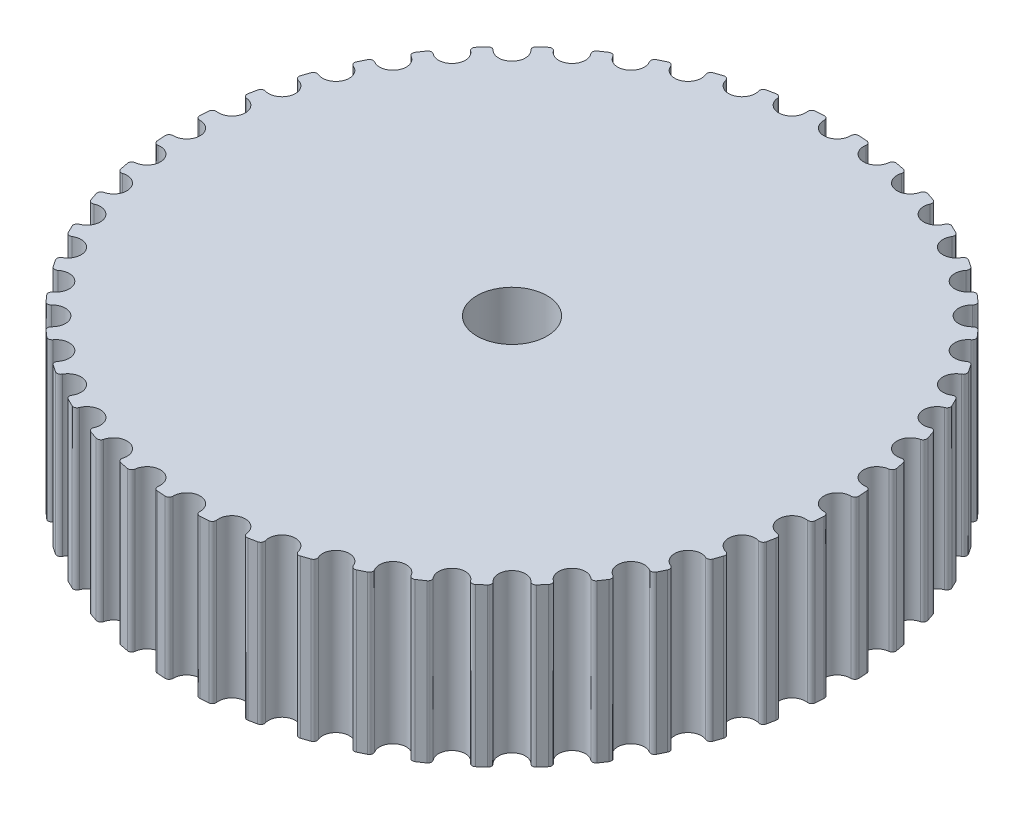
SolidWorks part; units mm, degrees
ref_plane "Ebene vorne" through (0, 0, 0) normal (0, 0, 1) x (1, 0, 0)
ref_plane "Ebene oben" through (0, 0, 0) normal (0, 1, 0) x (1, 0, 0)
ref_plane "Ebene rechts" through (0, 0, 0) normal (1, 0, 0) x (0, 0, -1)
sketch "Skizze1" plane through (0, 0, 0) normal (0, 1, 0) x (1, 0, 0)
  line L0 (0, 0) -> (27482.8107, 0) construction
  line L1 (0, 0) -> (0, 27482.8107) construction
  line L2 (0, 0) -> (8.3206, 63.2012) construction
  line L3 (1.9824, 37.5727) -> (2.9388, 37.51)
  line L4 (6.8697, 36.9925) -> (7.8097, 36.8055)
  line L5 (11.6394, 35.7794) -> (12.547, 35.4713)
  line L6 (16.2099, 33.954) -> (17.0696, 33.5301)
  line L7 (20.5032, 31.5477) -> (21.3001, 31.0152)
  line L8 (24.4455, 28.6016) -> (25.1662, 27.9697)
  line L9 (27.9697, 25.1662) -> (28.6016, 24.4455)
  line L10 (31.0152, 21.3001) -> (31.5477, 20.5032)
  line L11 (33.5301, 17.0696) -> (33.954, 16.2099)
  line L12 (35.4713, 12.547) -> (35.7794, 11.6394)
  line L13 (36.8055, 7.8097) -> (36.9925, 6.8697)
  line L14 (37.51, 2.9388) -> (37.5727, 1.9824)
  line L15 (37.5727, -1.9824) -> (37.51, -2.9388)
  line L16 (36.9925, -6.8697) -> (36.8055, -7.8097)
  line L17 (35.7794, -11.6394) -> (35.4713, -12.547)
  line L18 (33.954, -16.2099) -> (33.5301, -17.0696)
  line L19 (31.5477, -20.5032) -> (31.0152, -21.3001)
  line L20 (28.6016, -24.4455) -> (27.9697, -25.1662)
  line L21 (25.1662, -27.9697) -> (24.4455, -28.6016)
  line L22 (21.3001, -31.0152) -> (20.5032, -31.5477)
  line L23 (17.0696, -33.5301) -> (16.2099, -33.954)
  line L24 (12.547, -35.4713) -> (11.6394, -35.7794)
  line L25 (7.8097, -36.8055) -> (6.8697, -36.9925)
  line L26 (2.9388, -37.51) -> (1.9824, -37.5727)
  line L27 (-1.9824, -37.5727) -> (-2.9388, -37.51)
  line L28 (-6.8697, -36.9925) -> (-7.8097, -36.8055)
  line L29 (-11.6394, -35.7794) -> (-12.547, -35.4713)
  line L30 (-16.2099, -33.954) -> (-17.0696, -33.5301)
  line L31 (-20.5032, -31.5477) -> (-21.3001, -31.0152)
  line L32 (-24.4455, -28.6016) -> (-25.1662, -27.9697)
  line L33 (-27.9697, -25.1662) -> (-28.6016, -24.4455)
  line L34 (-31.0152, -21.3001) -> (-31.5477, -20.5032)
  line L35 (-33.5301, -17.0696) -> (-33.954, -16.2099)
  line L36 (-35.4713, -12.547) -> (-35.7794, -11.6394)
  line L37 (-36.8055, -7.8097) -> (-36.9925, -6.8697)
  line L38 (-37.51, -2.9388) -> (-37.5727, -1.9824)
  line L39 (-37.5727, 1.9824) -> (-37.51, 2.9388)
  line L40 (-36.9925, 6.8697) -> (-36.8055, 7.8097)
  line L41 (-35.7794, 11.6394) -> (-35.4713, 12.547)
  line L42 (-33.954, 16.2099) -> (-33.5301, 17.0696)
  line L43 (-31.5477, 20.5032) -> (-31.0152, 21.3001)
  line L44 (-28.6016, 24.4455) -> (-27.9697, 25.1662)
  line L45 (-25.1662, 27.9697) -> (-24.4455, 28.6016)
  line L46 (-21.3001, 31.0152) -> (-20.5032, 31.5477)
  line L47 (-17.0696, 33.5301) -> (-16.2099, 33.954)
  line L48 (-12.547, 35.4713) -> (-11.6394, 35.7794)
  line L49 (-7.8097, 36.8055) -> (-6.8697, 36.9925)
  line L50 (-2.9388, 37.51) -> (-1.9824, 37.5727)
  circle A0 centre (0, 0) radius 37.625 construction
  circle A1 centre (0, 0) radius 35.565 construction
  arc A2 (0, 35.565) -> (1.5244, 37.1318) centre (0, 37.09) ccw
  arc A3 (1.9824, 37.5727) -> (1.5244, 37.1318) centre (1.9543, 37.1436) ccw
  arc A4 (3.3353, 37.0131) -> (4.6422, 35.2607) centre (4.8412, 36.7727) ccw
  arc A5 (3.3353, 37.0131) -> (2.9388, 37.51) centre (2.9107, 37.0809) ccw
  arc A6 (8.1379, 36.2611) -> (9.2049, 34.3532) centre (9.5996, 35.8262) ccw
  arc A7 (8.1379, 36.2611) -> (7.8097, 36.8055) centre (7.7258, 36.3838) ccw
  arc A8 (6.8697, 36.9925) -> (6.3581, 36.6152) centre (6.7858, 36.5708) ccw
  arc A9 (4.6422, 35.2607) -> (6.3581, 36.6152) centre (4.8412, 36.7727) ccw
  arc A10 (12.8014, 34.8887) -> (13.6101, 32.8578) centre (14.1937, 34.2667) ccw
  arc A11 (12.8014, 34.8887) -> (12.547, 35.4713) centre (12.4087, 35.0641) ccw
  arc A12 (11.6394, 35.7794) -> (11.0829, 35.472) centre (11.5012, 35.3722) ccw
  arc A13 (9.2049, 34.3532) -> (11.0829, 35.472) centre (9.5996, 35.8262) ccw
  arc A14 (17.2457, 32.9193) -> (17.7825, 30.8002) centre (18.545, 32.1209) ccw
  arc A15 (17.2457, 32.9193) -> (17.0696, 33.5301) centre (16.8794, 33.1445) ccw
  arc A16 (16.2099, 33.954) -> (15.6181, 33.722) centre (16.0198, 33.5684) ccw
  arc A17 (13.6101, 32.8578) -> (15.6181, 33.722) centre (14.1937, 34.2667) ccw
  arc A18 (21.395, 30.3867) -> (21.6506, 28.2156) centre (22.579, 29.4255) ccw
  arc A19 (21.395, 30.3867) -> (21.3001, 31.0152) centre (21.0612, 30.6577) ccw
  arc A20 (20.5032, 31.5477) -> (19.8861, 31.3949) centre (20.2643, 31.1902) ccw
  arc A21 (17.7825, 30.8002) -> (19.8861, 31.3949) centre (18.545, 32.1209) ccw
  arc A22 (25.1782, 27.3341) -> (25.1483, 25.1483) centre (26.2266, 26.2266) ccw
  arc A23 (25.1782, 27.3341) -> (25.1662, 27.9697) centre (24.8826, 27.6464) ccw
  arc A24 (24.4455, 28.6016) -> (23.8138, 28.5306) centre (24.162, 28.2783) ccw
  arc A25 (21.6506, 28.2156) -> (23.8138, 28.5306) centre (22.579, 29.4255) ccw
  arc A26 (28.5306, 23.8138) -> (28.2156, 21.6506) centre (29.4255, 22.579) ccw
  arc A27 (28.5306, 23.8138) -> (28.6016, 24.4455) centre (28.2783, 24.162) ccw
  arc A28 (27.9697, 25.1662) -> (27.3341, 25.1782) centre (27.6464, 24.8826) ccw
  arc A29 (25.1483, 25.1483) -> (27.3341, 25.1782) centre (26.2266, 26.2266) ccw
  arc A30 (31.3949, 19.8861) -> (30.8002, 17.7825) centre (32.1209, 18.545) ccw
  arc A31 (31.3949, 19.8861) -> (31.5477, 20.5032) centre (31.1902, 20.2643) ccw
  arc A32 (31.0152, 21.3001) -> (30.3867, 21.395) centre (30.6577, 21.0612) ccw
  arc A33 (28.2156, 21.6506) -> (30.3867, 21.395) centre (29.4255, 22.579) ccw
  arc A34 (33.722, 15.6181) -> (32.8578, 13.6101) centre (34.2667, 14.1937) ccw
  arc A35 (33.722, 15.6181) -> (33.954, 16.2099) centre (33.5684, 16.0198) ccw
  arc A36 (33.5301, 17.0696) -> (32.9193, 17.2457) centre (33.1445, 16.8794) ccw
  arc A37 (30.8002, 17.7825) -> (32.9193, 17.2457) centre (32.1209, 18.545) ccw
  arc A38 (35.472, 11.0829) -> (34.3532, 9.2049) centre (35.8262, 9.5996) ccw
  arc A39 (35.472, 11.0829) -> (35.7794, 11.6394) centre (35.3722, 11.5012) ccw
  arc A40 (35.4713, 12.547) -> (34.8887, 12.8014) centre (35.0641, 12.4087) ccw
  arc A41 (32.8578, 13.6101) -> (34.8887, 12.8014) centre (34.2667, 14.1937) ccw
  arc A42 (36.6152, 6.3581) -> (35.2607, 4.6422) centre (36.7727, 4.8412) ccw
  arc A43 (36.6152, 6.3581) -> (36.9925, 6.8697) centre (36.5708, 6.7858) ccw
  arc A44 (36.8055, 7.8097) -> (36.2611, 8.1379) centre (36.3838, 7.7258) ccw
  arc A45 (34.3532, 9.2049) -> (36.2611, 8.1379) centre (35.8262, 9.5996) ccw
  arc A46 (37.1318, 1.5244) -> (35.565, 0) centre (37.09, 0) ccw
  arc A47 (37.1318, 1.5244) -> (37.5727, 1.9824) centre (37.1436, 1.9543) ccw
  arc A48 (37.51, 2.9388) -> (37.0131, 3.3353) centre (37.0809, 2.9107) ccw
  arc A49 (35.2607, 4.6422) -> (37.0131, 3.3353) centre (36.7727, 4.8412) ccw
  arc A50 (37.0131, -3.3353) -> (35.2607, -4.6422) centre (36.7727, -4.8412) ccw
  arc A51 (37.0131, -3.3353) -> (37.51, -2.9388) centre (37.0809, -2.9107) ccw
  arc A52 (37.5727, -1.9824) -> (37.1318, -1.5244) centre (37.1436, -1.9543) ccw
  arc A53 (35.565, 0) -> (37.1318, -1.5244) centre (37.09, 0) ccw
  arc A54 (36.2611, -8.1379) -> (34.3532, -9.2049) centre (35.8262, -9.5996) ccw
  arc A55 (36.2611, -8.1379) -> (36.8055, -7.8097) centre (36.3838, -7.7258) ccw
  arc A56 (36.9925, -6.8697) -> (36.6152, -6.3581) centre (36.5708, -6.7858) ccw
  arc A57 (35.2607, -4.6422) -> (36.6152, -6.3581) centre (36.7727, -4.8412) ccw
  arc A58 (34.8887, -12.8014) -> (32.8578, -13.6101) centre (34.2667, -14.1937) ccw
  arc A59 (34.8887, -12.8014) -> (35.4713, -12.547) centre (35.0641, -12.4087) ccw
  arc A60 (35.7794, -11.6394) -> (35.472, -11.0829) centre (35.3722, -11.5012) ccw
  arc A61 (34.3532, -9.2049) -> (35.472, -11.0829) centre (35.8262, -9.5996) ccw
  arc A62 (32.9193, -17.2457) -> (30.8002, -17.7825) centre (32.1209, -18.545) ccw
  arc A63 (32.9193, -17.2457) -> (33.5301, -17.0696) centre (33.1445, -16.8794) ccw
  arc A64 (33.954, -16.2099) -> (33.722, -15.6181) centre (33.5684, -16.0198) ccw
  arc A65 (32.8578, -13.6101) -> (33.722, -15.6181) centre (34.2667, -14.1937) ccw
  arc A66 (30.3867, -21.395) -> (28.2156, -21.6506) centre (29.4255, -22.579) ccw
  arc A67 (30.3867, -21.395) -> (31.0152, -21.3001) centre (30.6577, -21.0612) ccw
  arc A68 (31.5477, -20.5032) -> (31.3949, -19.8861) centre (31.1902, -20.2643) ccw
  arc A69 (30.8002, -17.7825) -> (31.3949, -19.8861) centre (32.1209, -18.545) ccw
  arc A70 (27.3341, -25.1782) -> (25.1483, -25.1483) centre (26.2266, -26.2266) ccw
  arc A71 (27.3341, -25.1782) -> (27.9697, -25.1662) centre (27.6464, -24.8826) ccw
  arc A72 (28.6016, -24.4455) -> (28.5306, -23.8138) centre (28.2783, -24.162) ccw
  arc A73 (28.2156, -21.6506) -> (28.5306, -23.8138) centre (29.4255, -22.579) ccw
  arc A74 (23.8138, -28.5306) -> (21.6506, -28.2156) centre (22.579, -29.4255) ccw
  arc A75 (23.8138, -28.5306) -> (24.4455, -28.6016) centre (24.162, -28.2783) ccw
  arc A76 (25.1662, -27.9697) -> (25.1782, -27.3341) centre (24.8826, -27.6464) ccw
  arc A77 (25.1483, -25.1483) -> (25.1782, -27.3341) centre (26.2266, -26.2266) ccw
  arc A78 (19.8861, -31.3949) -> (17.7825, -30.8002) centre (18.545, -32.1209) ccw
  arc A79 (19.8861, -31.3949) -> (20.5032, -31.5477) centre (20.2643, -31.1902) ccw
  arc A80 (21.3001, -31.0152) -> (21.395, -30.3867) centre (21.0612, -30.6577) ccw
  arc A81 (21.6506, -28.2156) -> (21.395, -30.3867) centre (22.579, -29.4255) ccw
  arc A82 (15.6181, -33.722) -> (13.6101, -32.8578) centre (14.1937, -34.2667) ccw
  arc A83 (15.6181, -33.722) -> (16.2099, -33.954) centre (16.0198, -33.5684) ccw
  arc A84 (17.0696, -33.5301) -> (17.2457, -32.9193) centre (16.8794, -33.1445) ccw
  arc A85 (17.7825, -30.8002) -> (17.2457, -32.9193) centre (18.545, -32.1209) ccw
  arc A86 (11.0829, -35.472) -> (9.2049, -34.3532) centre (9.5996, -35.8262) ccw
  arc A87 (11.0829, -35.472) -> (11.6394, -35.7794) centre (11.5012, -35.3722) ccw
  arc A88 (12.547, -35.4713) -> (12.8014, -34.8887) centre (12.4087, -35.0641) ccw
  arc A89 (13.6101, -32.8578) -> (12.8014, -34.8887) centre (14.1937, -34.2667) ccw
  arc A90 (6.3581, -36.6152) -> (4.6422, -35.2607) centre (4.8412, -36.7727) ccw
  arc A91 (6.3581, -36.6152) -> (6.8697, -36.9925) centre (6.7858, -36.5708) ccw
  arc A92 (7.8097, -36.8055) -> (8.1379, -36.2611) centre (7.7258, -36.3838) ccw
  arc A93 (9.2049, -34.3532) -> (8.1379, -36.2611) centre (9.5996, -35.8262) ccw
  arc A94 (1.5244, -37.1318) -> (0, -35.565) centre (0, -37.09) ccw
  arc A95 (1.5244, -37.1318) -> (1.9824, -37.5727) centre (1.9543, -37.1436) ccw
  arc A96 (2.9388, -37.51) -> (3.3353, -37.0131) centre (2.9107, -37.0809) ccw
  arc A97 (4.6422, -35.2607) -> (3.3353, -37.0131) centre (4.8412, -36.7727) ccw
  arc A98 (-3.3353, -37.0131) -> (-4.6422, -35.2607) centre (-4.8412, -36.7727) ccw
  arc A99 (-3.3353, -37.0131) -> (-2.9388, -37.51) centre (-2.9107, -37.0809) ccw
  arc A100 (-1.9824, -37.5727) -> (-1.5244, -37.1318) centre (-1.9543, -37.1436) ccw
  arc A101 (0, -35.565) -> (-1.5244, -37.1318) centre (0, -37.09) ccw
  arc A102 (-8.1379, -36.2611) -> (-9.2049, -34.3532) centre (-9.5996, -35.8262) ccw
  arc A103 (-8.1379, -36.2611) -> (-7.8097, -36.8055) centre (-7.7258, -36.3838) ccw
  arc A104 (-6.8697, -36.9925) -> (-6.3581, -36.6152) centre (-6.7858, -36.5708) ccw
  arc A105 (-4.6422, -35.2607) -> (-6.3581, -36.6152) centre (-4.8412, -36.7727) ccw
  arc A106 (-12.8014, -34.8887) -> (-13.6101, -32.8578) centre (-14.1937, -34.2667) ccw
  arc A107 (-12.8014, -34.8887) -> (-12.547, -35.4713) centre (-12.4087, -35.0641) ccw
  arc A108 (-11.6394, -35.7794) -> (-11.0829, -35.472) centre (-11.5012, -35.3722) ccw
  arc A109 (-9.2049, -34.3532) -> (-11.0829, -35.472) centre (-9.5996, -35.8262) ccw
  arc A110 (-17.2457, -32.9193) -> (-17.7825, -30.8002) centre (-18.545, -32.1209) ccw
  arc A111 (-17.2457, -32.9193) -> (-17.0696, -33.5301) centre (-16.8794, -33.1445) ccw
  arc A112 (-16.2099, -33.954) -> (-15.6181, -33.722) centre (-16.0198, -33.5684) ccw
  arc A113 (-13.6101, -32.8578) -> (-15.6181, -33.722) centre (-14.1937, -34.2667) ccw
  arc A114 (-21.395, -30.3867) -> (-21.6506, -28.2156) centre (-22.579, -29.4255) ccw
  arc A115 (-21.395, -30.3867) -> (-21.3001, -31.0152) centre (-21.0612, -30.6577) ccw
  arc A116 (-20.5032, -31.5477) -> (-19.8861, -31.3949) centre (-20.2643, -31.1902) ccw
  arc A117 (-17.7825, -30.8002) -> (-19.8861, -31.3949) centre (-18.545, -32.1209) ccw
  arc A118 (-25.1782, -27.3341) -> (-25.1483, -25.1483) centre (-26.2266, -26.2266) ccw
  arc A119 (-25.1782, -27.3341) -> (-25.1662, -27.9697) centre (-24.8826, -27.6464) ccw
  arc A120 (-24.4455, -28.6016) -> (-23.8138, -28.5306) centre (-24.162, -28.2783) ccw
  arc A121 (-21.6506, -28.2156) -> (-23.8138, -28.5306) centre (-22.579, -29.4255) ccw
  arc A122 (-28.5306, -23.8138) -> (-28.2156, -21.6506) centre (-29.4255, -22.579) ccw
  arc A123 (-28.5306, -23.8138) -> (-28.6016, -24.4455) centre (-28.2783, -24.162) ccw
  arc A124 (-27.9697, -25.1662) -> (-27.3341, -25.1782) centre (-27.6464, -24.8826) ccw
  arc A125 (-25.1483, -25.1483) -> (-27.3341, -25.1782) centre (-26.2266, -26.2266) ccw
  arc A126 (-31.3949, -19.8861) -> (-30.8002, -17.7825) centre (-32.1209, -18.545) ccw
  arc A127 (-31.3949, -19.8861) -> (-31.5477, -20.5032) centre (-31.1902, -20.2643) ccw
  arc A128 (-31.0152, -21.3001) -> (-30.3867, -21.395) centre (-30.6577, -21.0612) ccw
  arc A129 (-28.2156, -21.6506) -> (-30.3867, -21.395) centre (-29.4255, -22.579) ccw
  arc A130 (-33.722, -15.6181) -> (-32.8578, -13.6101) centre (-34.2667, -14.1937) ccw
  arc A131 (-33.722, -15.6181) -> (-33.954, -16.2099) centre (-33.5684, -16.0198) ccw
  arc A132 (-33.5301, -17.0696) -> (-32.9193, -17.2457) centre (-33.1445, -16.8794) ccw
  arc A133 (-30.8002, -17.7825) -> (-32.9193, -17.2457) centre (-32.1209, -18.545) ccw
  arc A134 (-35.472, -11.0829) -> (-34.3532, -9.2049) centre (-35.8262, -9.5996) ccw
  arc A135 (-35.472, -11.0829) -> (-35.7794, -11.6394) centre (-35.3722, -11.5012) ccw
  arc A136 (-35.4713, -12.547) -> (-34.8887, -12.8014) centre (-35.0641, -12.4087) ccw
  arc A137 (-32.8578, -13.6101) -> (-34.8887, -12.8014) centre (-34.2667, -14.1937) ccw
  arc A138 (-36.6152, -6.3581) -> (-35.2607, -4.6422) centre (-36.7727, -4.8412) ccw
  arc A139 (-36.6152, -6.3581) -> (-36.9925, -6.8697) centre (-36.5708, -6.7858) ccw
  arc A140 (-36.8055, -7.8097) -> (-36.2611, -8.1379) centre (-36.3838, -7.7258) ccw
  arc A141 (-34.3532, -9.2049) -> (-36.2611, -8.1379) centre (-35.8262, -9.5996) ccw
  arc A142 (-37.1318, -1.5244) -> (-35.565, 0) centre (-37.09, 0) ccw
  arc A143 (-37.1318, -1.5244) -> (-37.5727, -1.9824) centre (-37.1436, -1.9543) ccw
  arc A144 (-37.51, -2.9388) -> (-37.0131, -3.3353) centre (-37.0809, -2.9107) ccw
  arc A145 (-35.2607, -4.6422) -> (-37.0131, -3.3353) centre (-36.7727, -4.8412) ccw
  arc A146 (-37.0131, 3.3353) -> (-35.2607, 4.6422) centre (-36.7727, 4.8412) ccw
  arc A147 (-37.0131, 3.3353) -> (-37.51, 2.9388) centre (-37.0809, 2.9107) ccw
  arc A148 (-37.5727, 1.9824) -> (-37.1318, 1.5244) centre (-37.1436, 1.9543) ccw
  arc A149 (-35.565, 0) -> (-37.1318, 1.5244) centre (-37.09, 0) ccw
  arc A150 (-36.2611, 8.1379) -> (-34.3532, 9.2049) centre (-35.8262, 9.5996) ccw
  arc A151 (-36.2611, 8.1379) -> (-36.8055, 7.8097) centre (-36.3838, 7.7258) ccw
  arc A152 (-36.9925, 6.8697) -> (-36.6152, 6.3581) centre (-36.5708, 6.7858) ccw
  arc A153 (-35.2607, 4.6422) -> (-36.6152, 6.3581) centre (-36.7727, 4.8412) ccw
  arc A154 (-34.8887, 12.8014) -> (-32.8578, 13.6101) centre (-34.2667, 14.1937) ccw
  arc A155 (-34.8887, 12.8014) -> (-35.4713, 12.547) centre (-35.0641, 12.4087) ccw
  arc A156 (-35.7794, 11.6394) -> (-35.472, 11.0829) centre (-35.3722, 11.5012) ccw
  arc A157 (-34.3532, 9.2049) -> (-35.472, 11.0829) centre (-35.8262, 9.5996) ccw
  arc A158 (-32.9193, 17.2457) -> (-30.8002, 17.7825) centre (-32.1209, 18.545) ccw
  arc A159 (-32.9193, 17.2457) -> (-33.5301, 17.0696) centre (-33.1445, 16.8794) ccw
  arc A160 (-33.954, 16.2099) -> (-33.722, 15.6181) centre (-33.5684, 16.0198) ccw
  arc A161 (-32.8578, 13.6101) -> (-33.722, 15.6181) centre (-34.2667, 14.1937) ccw
  arc A162 (-30.3867, 21.395) -> (-28.2156, 21.6506) centre (-29.4255, 22.579) ccw
  arc A163 (-30.3867, 21.395) -> (-31.0152, 21.3001) centre (-30.6577, 21.0612) ccw
  arc A164 (-31.5477, 20.5032) -> (-31.3949, 19.8861) centre (-31.1902, 20.2643) ccw
  arc A165 (-30.8002, 17.7825) -> (-31.3949, 19.8861) centre (-32.1209, 18.545) ccw
  arc A166 (-27.3341, 25.1782) -> (-25.1483, 25.1483) centre (-26.2266, 26.2266) ccw
  arc A167 (-27.3341, 25.1782) -> (-27.9697, 25.1662) centre (-27.6464, 24.8826) ccw
  arc A168 (-28.6016, 24.4455) -> (-28.5306, 23.8138) centre (-28.2783, 24.162) ccw
  arc A169 (-28.2156, 21.6506) -> (-28.5306, 23.8138) centre (-29.4255, 22.579) ccw
  arc A170 (-23.8138, 28.5306) -> (-21.6506, 28.2156) centre (-22.579, 29.4255) ccw
  arc A171 (-23.8138, 28.5306) -> (-24.4455, 28.6016) centre (-24.162, 28.2783) ccw
  arc A172 (-25.1662, 27.9697) -> (-25.1782, 27.3341) centre (-24.8826, 27.6464) ccw
  arc A173 (-25.1483, 25.1483) -> (-25.1782, 27.3341) centre (-26.2266, 26.2266) ccw
  arc A174 (-19.8861, 31.3949) -> (-17.7825, 30.8002) centre (-18.545, 32.1209) ccw
  arc A175 (-19.8861, 31.3949) -> (-20.5032, 31.5477) centre (-20.2643, 31.1902) ccw
  arc A176 (-21.3001, 31.0152) -> (-21.395, 30.3867) centre (-21.0612, 30.6577) ccw
  arc A177 (-21.6506, 28.2156) -> (-21.395, 30.3867) centre (-22.579, 29.4255) ccw
  arc A178 (-15.6181, 33.722) -> (-13.6101, 32.8578) centre (-14.1937, 34.2667) ccw
  arc A179 (-15.6181, 33.722) -> (-16.2099, 33.954) centre (-16.0198, 33.5684) ccw
  arc A180 (-17.0696, 33.5301) -> (-17.2457, 32.9193) centre (-16.8794, 33.1445) ccw
  arc A181 (-17.7825, 30.8002) -> (-17.2457, 32.9193) centre (-18.545, 32.1209) ccw
  arc A182 (-11.0829, 35.472) -> (-9.2049, 34.3532) centre (-9.5996, 35.8262) ccw
  arc A183 (-11.0829, 35.472) -> (-11.6394, 35.7794) centre (-11.5012, 35.3722) ccw
  arc A184 (-12.547, 35.4713) -> (-12.8014, 34.8887) centre (-12.4087, 35.0641) ccw
  arc A185 (-13.6101, 32.8578) -> (-12.8014, 34.8887) centre (-14.1937, 34.2667) ccw
  arc A186 (-6.3581, 36.6152) -> (-4.6422, 35.2607) centre (-4.8412, 36.7727) ccw
  arc A187 (-6.3581, 36.6152) -> (-6.8697, 36.9925) centre (-6.7858, 36.5708) ccw
  arc A188 (-7.8097, 36.8055) -> (-8.1379, 36.2611) centre (-7.7258, 36.3838) ccw
  arc A189 (-9.2049, 34.3532) -> (-8.1379, 36.2611) centre (-9.5996, 35.8262) ccw
  arc A190 (-1.5244, 37.1318) -> (0, 35.565) centre (0, 37.09) ccw
  arc A191 (-1.5244, 37.1318) -> (-1.9824, 37.5727) centre (-1.9543, 37.1436) ccw
  arc A192 (-2.9388, 37.51) -> (-3.3353, 37.0131) centre (-2.9107, 37.0809) ccw
  arc A193 (-4.6422, 35.2607) -> (-3.3353, 37.0131) centre (-4.8412, 36.7727) ccw
  point P492 (0, 0)
  dimension "D1" = 75.25
  dimension "D2" = 71.13
  dimension "D3" = 3.05
  dimension "D4" = 0.86
  dimension "D5" = 7.5
  dimension "D6" = 48
extrude "Aufsatz-Linear austragen1" add sketch "Skizze1" along normal blind 18
hole_wizard "Ø8.0 (8) Durchmesser Bohrung1" positions "Skizze3" profile "Skizze4" hole size "Ø8.0" standard "ISO" end condition through all
sketch "Skizze3" plane through (0, 18, 0) normal (0, 1, 0) x (1, 0, 0)
  point P0 (0, 0)
sketch "Skizze4" plane through (0, 18, 0) normal (1, 0, 0) x (0, 0, 1)
  line L0 (0, 0) -> (0, 18)
  line L1 (0, 18) -> (4, 18)
  line L2 (4, 18) -> (4, 0)
  line L5 (4, 0) -> (0, 0)
  line L11 (0, -6.35) -> (0, 107.95) construction
  dimension "Bohrerdurchmesser" = 8
  dimension "Bohrungstiefe" = 18
